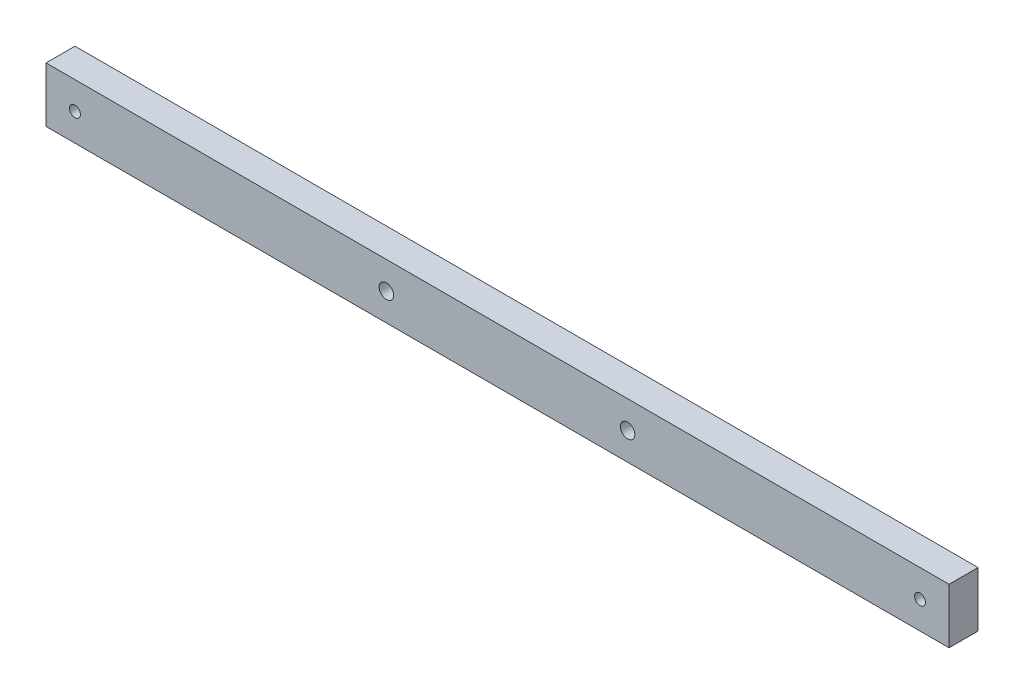
SolidWorks part; units mm, degrees
ref_plane "前视基准面" through (0, 0, 0) normal (0, 0, 1) x (1, 0, 0)
ref_plane "上视基准面" through (0, 0, 0) normal (0, 1, 0) x (1, 0, 0)
ref_plane "右视基准面" through (0, 0, 0) normal (1, 0, 0) x (0, 0, -1)
sketch "草图2" plane through (0, 0, 0) normal (0, 0, 1) x (1, 0, 0)
  line L0 (0, 0) -> (0, -11.1015) construction
  line L1 (-31.175, 1.9) -> (31.175, 1.9)
  line L2 (-31.175, 1.9) -> (-31.175, -1.9)
  line L3 (-31.175, -1.9) -> (31.175, -1.9)
  line L4 (31.175, 1.9) -> (31.175, -1.9)
  line L5 (-31.175, 1.9) -> (31.175, -1.9) construction
  line L6 (-31.175, -1.9) -> (31.175, 1.9) construction
  circle A1 centre (8.98, 0) radius 0.5
  circle A3 centre (-7.675, 0) radius 0.5
  point P0 (0, 0)
  dimension "D3" = 1
  dimension "D5" = 1
  dimension "D4" = 8.98
  dimension "D1" = 3.8
  dimension "D2" = 62.35
  dimension "D6" = 23.5
extrude "凸台-拉伸1" add sketch "草图2" along normal blind 2
sketch "草图3" plane through (0, 0, 0) normal (0, 0, -1) x (-1, 0, 0)
  line L0 (31.175, 1.9) -> (31.175, -1.9) construction
  line L1 (31.175, -1.9) -> (-31.175, -1.9) construction
  line L2 (-31.175, 1.9) -> (31.175, 1.9) construction
  line L3 (29.175, -1.9) -> (29.175, 1.9) construction
  line L4 (-31.175, 0) -> (-29.175, 0) construction
  line L5 (-31.175, -1.9) -> (-31.175, 1.9) construction
  circle A0 centre (29.175, 0) radius 0.375
  circle A1 centre (-29.175, 0) radius 0.375
  dimension "D1" = 0.75
  dimension "D3" = 0.75
  dimension "D2" = 2
  dimension "D4" = 2
extrude "切除-拉伸1" cut sketch "草图3" against normal up to next
